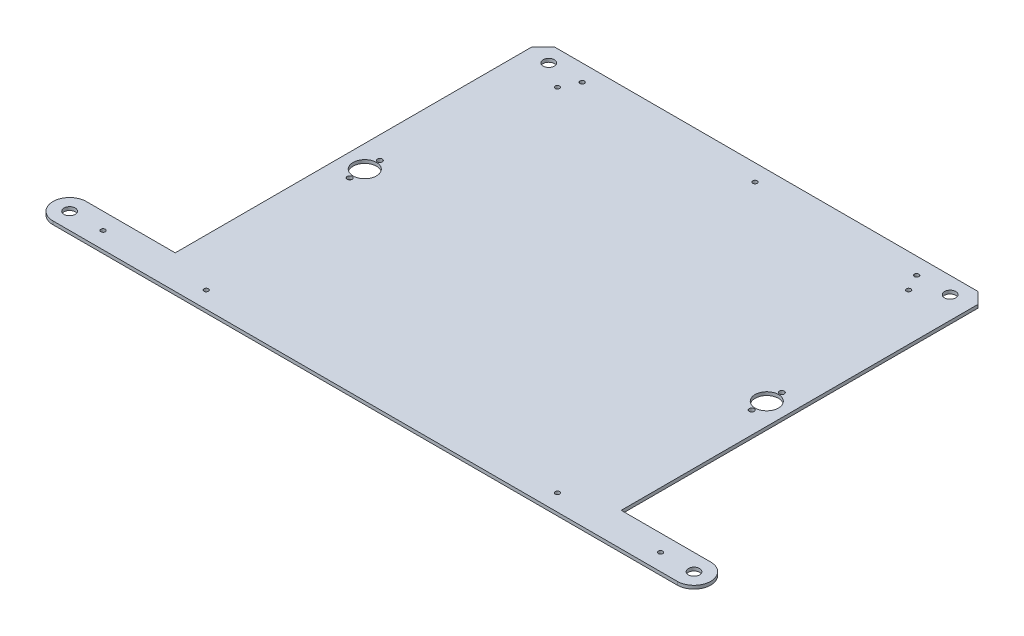
SolidWorks part; units mm, degrees
ref_plane "Front Plane" through (0, 0, 0) normal (0, 0, 1) x (1, 0, 0)
ref_plane "Top Plane" through (0, 0, 0) normal (0, 1, 0) x (1, 0, 0)
ref_plane "Right Plane" through (0, 0, 0) normal (1, 0, 0) x (0, 0, -1)
sketch "Sketch1" plane through (0, 0, 0) normal (0, 1, 0) x (1, 0, 0)
  line L0 (0, 0) -> (0, -157.5) construction
  line L1 (0, -157.5) -> (-280, -157.5) construction
  line L2 (0, -157.5) -> (280, -157.5) construction
  line L3 (-200.2852, -142.5) -> (199.7148, -142.5) construction
  line L4 (-200.2852, -142.5) -> (-280, -142.5)
  line L5 (-157.5, 157.5) -> (157.5, -157.5) construction
  line L6 (-157.5, -157.5) -> (157.5, 157.5) construction
  line L7 (-200.2852, -142.5) -> (-200.2852, 187.5)
  line L8 (-200.2852, 187.5) -> (199.7148, 187.5)
  line L9 (199.7148, 187.5) -> (199.7148, -142.5)
  line L10 (-280, -172.5) -> (280, -172.5)
  line L11 (-180.2852, 172.5) -> (-180.2852, -157.5) construction
  line L12 (280, -142.5) -> (199.7148, -142.5)
  circle A0 centre (-157.5, 157.5) radius 2
  circle A1 centre (157.5, 157.5) radius 2
  circle A2 centre (157.5, -157.5) radius 2
  circle A3 centre (-157.5, -157.5) radius 2
  circle A4 centre (-280, -157.5) radius 5
  circle A5 centre (280, -157.5) radius 5
  arc A6 (-280, -142.5) -> (-280, -172.5) centre (-280, -157.5) ccw
  arc A7 (280, -172.5) -> (280, -142.5) centre (280, -157.5) ccw
  circle A8 centre (-250, -157.5) radius 2
  circle A9 centre (250, -157.5) radius 2
  circle A10 centre (-180.2852, 172.5) radius 5
  circle A11 centre (179.7148, 172.5) radius 5
  circle A12 centre (-150.2852, 172.5) radius 2
  circle A13 centre (4.7148, 172.5) radius 2
  circle A14 centre (149.7148, 172.5) radius 2
  circle A15 centre (-180.2852, 7.5) radius 10.5
  circle A16 centre (-180.2852, 21) radius 2.25
  circle A17 centre (-180.2852, -6) radius 2.25
  circle A18 centre (180.2852, -6) radius 2.25
  circle A19 centre (180.2852, 21) radius 2.25
  circle A20 centre (180.2852, 7.5) radius 10.5
  point P0 (0, 0)
  point P53 (0, 0)
  dimension "D3" = 445.4773
  dimension "D2" = 4
  dimension "D6" = 10
  dimension "D8" = 30
  dimension "D18" = 21
  dimension "D21" = 4.5
  dimension "D1" = 315
  dimension "D4" = 445.4773
  dimension "D9" = 30
  dimension "D10" = 400
  dimension "D11" = 20
  dimension "D12" = 15
  dimension "D13" = 15
  dimension "D14" = 20
  dimension "D15" = 30
  dimension "D16" = 30
  dimension "D17" = 330
  dimension "D19" = 27
  dimension "D20" = 13.5
  dimension "D23" = 280
extrude "Boss-Extrude1" add sketch "Sketch1" along normal blind 3
chamfer "Chamfer1" distance 10 angle 45 2 edges at (199.7148, 1.5, -187.5) (-200.2852, 1.5, -187.5)
chamfer "Chamfer2" distance 40 angle 45 rebuild error yes
